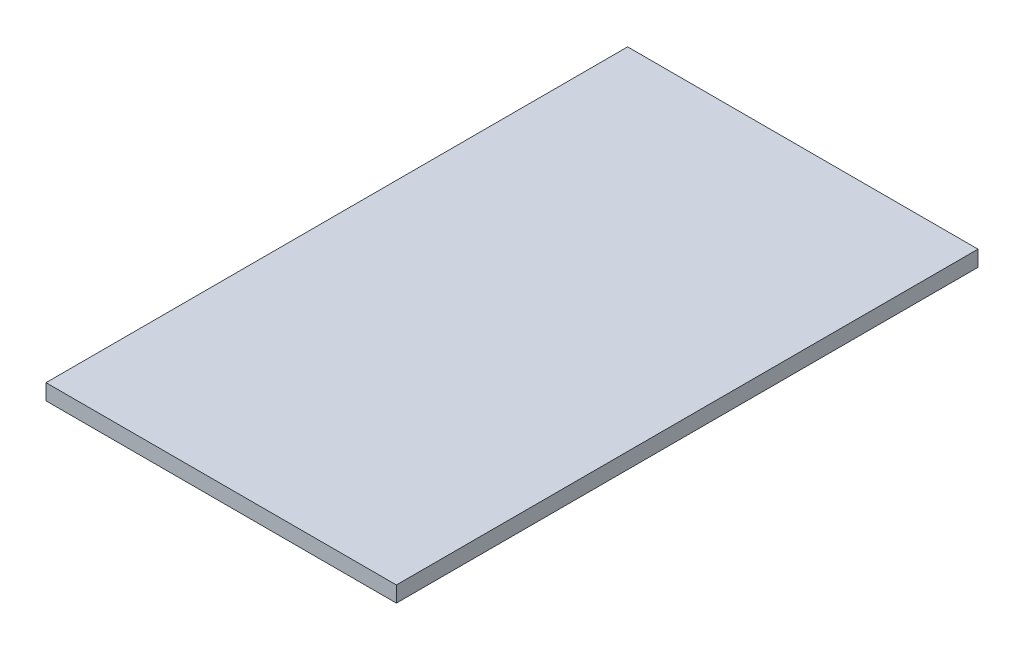
SolidWorks part; units mm, degrees
ref_plane "Front Plane" through (0, 0, 0) normal (0, 0, 1) x (1, 0, 0)
ref_plane "Top Plane" through (0, 0, 0) normal (0, 1, 0) x (1, 0, 0)
ref_plane "Right Plane" through (0, 0, 0) normal (1, 0, 0) x (0, 0, -1)
sketch "Sketch1" plane through (0, 0, 0) normal (0, 1, 0) x (1, 0, 0)
  line L1 (-50, -83) -> (50, -83)
  line L2 (-50, -83) -> (-50, 83)
  line L3 (-50, 83) -> (50, 83)
  line L4 (50, -83) -> (50, 83)
  line L5 (-50, -83) -> (50, 83) construction
  line L6 (-50, 83) -> (50, -83) construction
  point P0 (0, 0)
  dimension "D1" = 166
  dimension "D2" = 100
extrude "MAIN BODY" add sketch "Sketch1" along normal blind 4.5
sketch "Sketch2" plane through (0, 0, 0) normal (0, -1, 0) x (1, 0, 0)
  line L0 (50, -83) -> (-50, -83) construction
  line L1 (-46, -83) -> (26, -83)
  line L2 (-46, -83) -> (-46, -43)
  line L3 (-46, -43) -> (26, -43)
  line L4 (26, -83) -> (26, -43)
  line L5 (-50, -83) -> (-50, 83) construction
  line L6 (50, 83) -> (50, -83) construction
  dimension "D1" = 4
  dimension "D2" = 24
  dimension "D3" = 40
extrude "PCBs AND SUCH" add sketch "Sketch2" along normal blind 5
